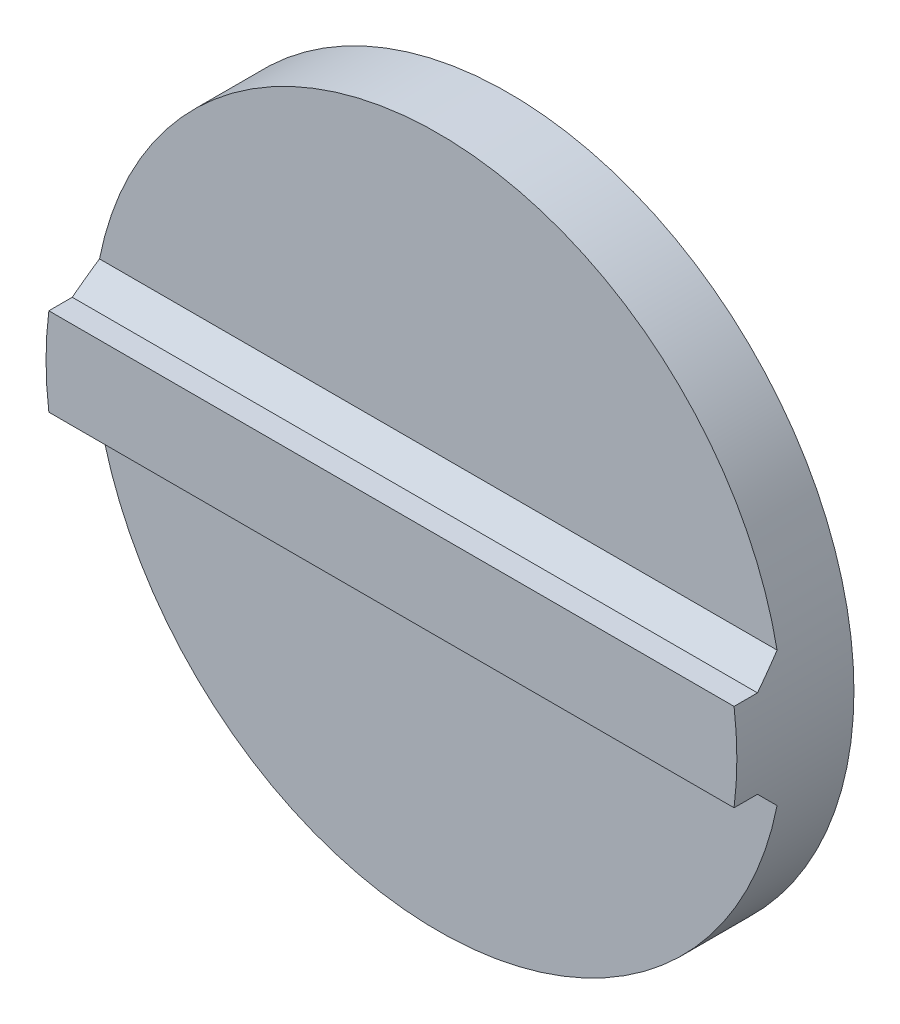
SolidWorks part; units mm, degrees
ref_plane "Front Plane" through (0, 0, 0) normal (0, 0, 1) x (1, 0, 0)
ref_plane "Top Plane" through (0, 0, 0) normal (0, 1, 0) x (1, 0, 0)
ref_plane "Right Plane" through (0, 0, 0) normal (1, 0, 0) x (0, 0, -1)
sketch "Sketch1" plane through (0, 0, 0) normal (0, 0, 1) x (1, 0, 0)
  circle A0 centre (0, 0) radius 5.9
  dimension "D1" = 11.8
extrude "Boss-Extrude1" add sketch "Sketch1" along normal blind 1.2
sketch "Sketch2" plane through (0, 0, 1.2) normal (0, 0, 1) x (1, 0, 0)
  line L0 (0, 0.75) -> (0, -0.75) construction
  line L1 (-5.8521, -0.75) -> (5.8521, -0.75)
  line L3 (-5.8521, 0.75) -> (5.8521, 0.75)
  circle A0 centre (0, 0) radius 5.9 construction
  arc A1 (-5.8521, 0.75) -> (-5.8521, -0.75) centre (0, 0) ccw
  arc A2 (5.8521, -0.75) -> (5.8521, 0.75) centre (0, 0) ccw
  point P0 (0, 0)
  dimension "D1" = 1.5
extrude "Boss-Extrude2" add sketch "Sketch2" along normal blind 0.8
chamfer "Chamfer1" distance 0.4 2 edges at (0, -0.75, 1.2) (0, 0.75, 1.2)
sketch "Sketch3" plane through (0, 0, 0) normal (0, 0, -1) x (-1, 0, 0)
  circle A0 centre (0, 0) radius 1.5
  dimension "D1" = 3
extrude "Cut-Extrude1" cut sketch "Sketch3" against normal blind 0.5
